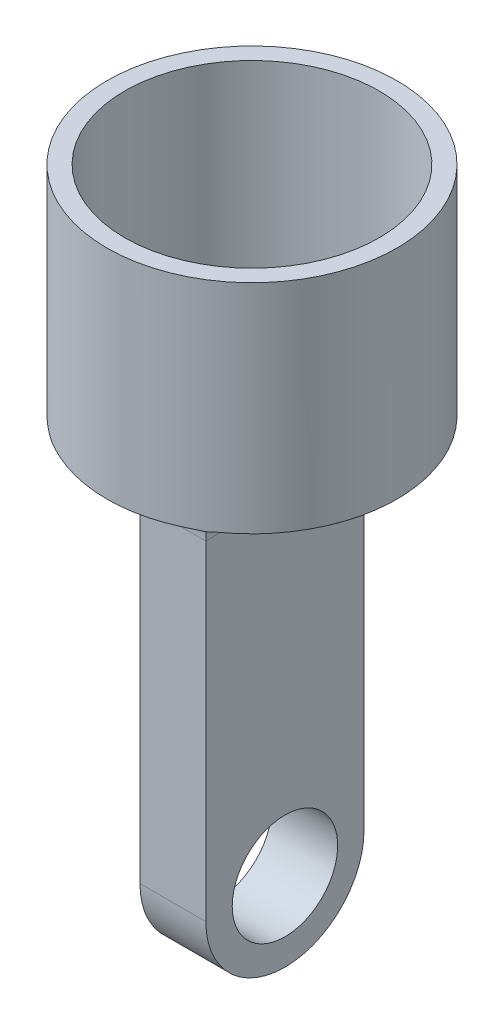
SolidWorks part; units mm, degrees
material "7075-T6 (SN)"
ref_plane "Front Plane" through (0, 0, 0) normal (0, 0, 1) x (1, 0, 0)
ref_plane "Top Plane" through (0, 0, 0) normal (0, 1, 0) x (1, 0, 0)
ref_plane "Right Plane" through (0, 0, 0) normal (1, 0, 0) x (0, 0, -1)
sketch "Sketch1" plane through (0, 0, 0) normal (0, 1, 0) x (1, 0, 0)
  circle A0 centre (0, 0) radius 11
  circle A1 centre (0, 0) radius 9.652
  dimension "D1" = 22
  dimension "D2" = 19.304
extrude "Boss-Extrude1" add sketch "Sketch1" along normal blind 15
sketch "Sketch2" plane through (0, 0, 0) normal (0, -1, 0) x (1, 0, 0)
  circle A0 centre (0, 0) radius 11
  circle A1 centre (0, 0) radius 11 construction
extrude "Boss-Extrude2" add sketch "Sketch2" along normal blind 1.5
sketch "Sketch4" plane through (0, -1.5, 0) normal (0, -1, 0) x (1, 0, 0)
  line L1 (-2.5, -6) -> (2.5, -6)
  line L2 (-2.5, -6) -> (-2.5, 6)
  line L3 (-2.5, 6) -> (2.5, 6)
  line L4 (2.5, -6) -> (2.5, 6)
  line L5 (-2.5, -6) -> (2.5, 6) construction
  line L6 (-2.5, 6) -> (2.5, -6) construction
  point P0 (0, 0)
  dimension "D1" = 5
  dimension "D2" = 6
extrude "Boss-Extrude4" add sketch "Sketch4" along normal blind 35
ref_plane "Plane1" through (0, 0, 0) normal (-1, 0, 0) x (0, 0, 1)
sketch "Sketch5" plane through (-2.5, 0, 0) normal (-1, 0, 0) x (0, 0, 1)
  line L0 (0, -1.5) -> (0, -36.5) construction
  line L2 (6, -1.5) -> (-6, -1.5) construction
  line L3 (6, -36.5) -> (-6, -36.5) construction
  line L4 (6, -36.5) -> (-6, -36.5) construction
  circle A0 centre (0, -30.5) radius 4
  dimension "D1" = 8
  dimension "D2" = 6
extrude "Cut-Extrude1" cut sketch "Sketch5" against normal up to surface (5 mm away) up to face at (2.5, -19, 0)
sketch "Sketch6" plane through (-2.5, 0, 0) normal (-1, 0, 0) x (0, 0, 1)
  line L0 (-6, -30.5) -> (-6, -36.5)
  line L2 (6, -36.5) -> (6, -1.5) construction
  line L3 (6, -36.5) -> (6, -30.5)
  line L4 (0, -34.5) -> (0, -36.5) construction
  arc A0 (-6, -36.5) -> (6, -36.5) centre (0, -30.5) ccw
  arc A1 (-6, -30.5) -> (6, -30.5) centre (0, -30.5) ccw
  circle A2 centre (0, -30.5) radius 4 construction
extrude "Cut-Extrude2" cut sketch "Sketch6" against normal through all contours A1 L3 A0 L0
fillet "Fillet1" radius 4 4 edges at (0, -1.5, -6) (2.5, -1.5, 0) (0, -1.5, 6) (-2.5, -1.5, 0)
sketch "Sketch7" plane through (2.5, 0, 0) normal (1, 0, 0) x (0, 0, -1)
  line L0 (0, -7.5) -> (0, -30.5) construction
  line L1 (-4, -7.5) -> (4, -7.5)
  line L2 (-4, -7.5) -> (-4, -26.0279)
  line L4 (4, -7.5) -> (4, -26.0279)
  line L7 (-6, -30.5) -> (-6, -5.5) construction
  line L8 (6, -5.5) -> (-6, -5.5) construction
  arc A0 (4, -26.0279) -> (-4, -26.0279) centre (0, -30.5) ccw
  dimension "D2" = 12
  dimension "D1" = 2
  dimension "D3" = 2
extrude "Cut-Extrude3" [suppressed] cut sketch "Sketch7" against normal up to surface (5 mm away)
fillet "Fillet2" [suppressed] radius 2
